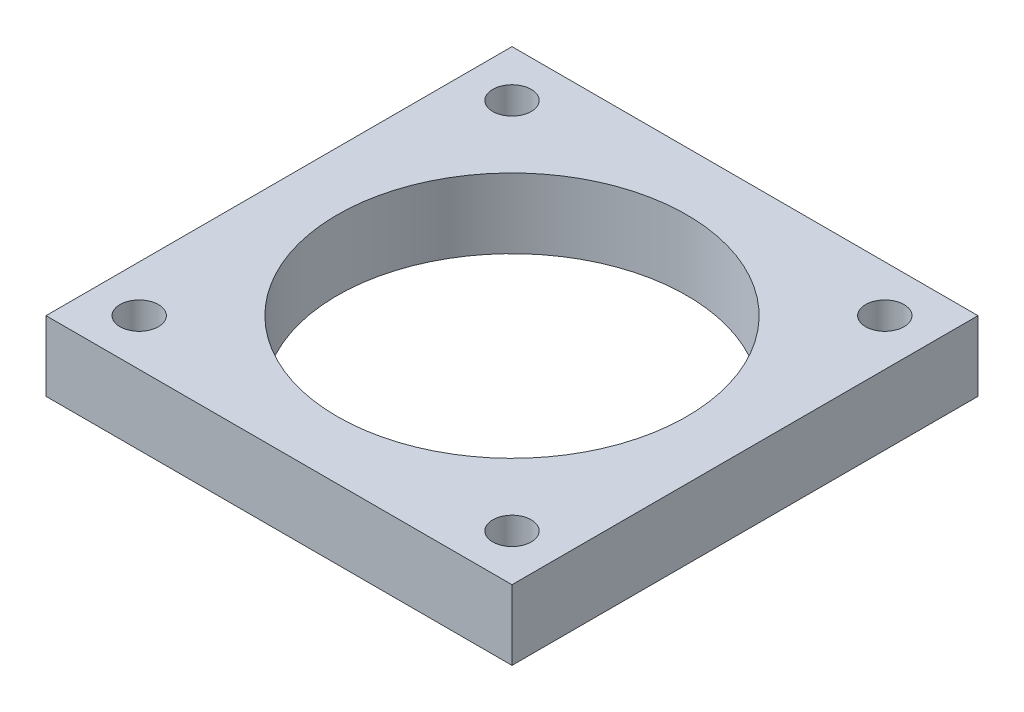
SolidWorks part; units mm, degrees
ref_plane "Front Plane" through (0, 0, 0) normal (0, 0, 1) x (1, 0, 0)
ref_plane "Top Plane" through (0, 0, 0) normal (0, 1, 0) x (1, 0, 0)
ref_plane "Right Plane" through (0, 0, 0) normal (1, 0, 0) x (0, 0, -1)
sketch "Sketch1" plane through (0, 0, 0) normal (0, 1, 0) x (1, 0, 0)
  line L0 (0, 40) -> (40, 0) construction
  line L1 (0, 0) -> (40, 0)
  line L2 (0, 0) -> (0, 40)
  line L3 (0, 40) -> (40, 40)
  line L4 (40, 0) -> (40, 40)
  line L6 (36, 36) -> (4, 36) construction
  line L7 (36, 36) -> (36, 4) construction
  line L8 (36, 4) -> (4, 4) construction
  line L9 (4, 36) -> (4, 4) construction
  line L10 (36, 36) -> (4, 4) construction
  line L11 (36, 4) -> (4, 36) construction
  circle A0 centre (4, 36) radius 1.651
  circle A1 centre (36, 36) radius 1.651
  circle A2 centre (4, 4) radius 1.651
  circle A3 centre (36, 4) radius 1.651
  circle A4 centre (20, 20) radius 15
  point P5 (20, 20)
  dimension "D4" = 30
  dimension "D5" = 3.302
  dimension "D1" = 40
  dimension "D2" = 40
  dimension "D3" = 32
extrude "Boss-Extrude1" add sketch "Sketch1" along normal blind 6
ref_plane "Plane1" through (20, 0, 0) normal (1, 0, 0) x (0, 0, -1)
ref_plane "Plane2" through (0, 0, -20) normal (0, 0, -1) x (-1, 0, 0)
equation "\"D2@Sketch1\"=\"D1@Sketch1\""
